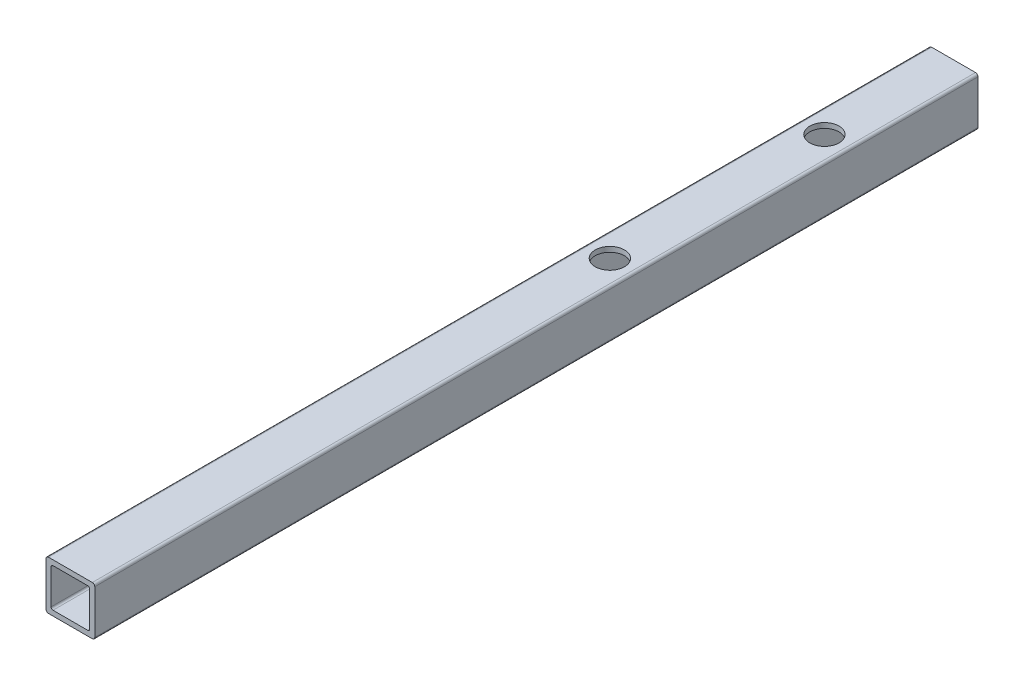
SolidWorks part; units mm, degrees
ref_plane "Front" through (0, 0, 0) normal (0, 0, 1) x (1, 0, 0)
ref_plane "Top" through (0, 0, 0) normal (0, 1, 0) x (1, 0, 0)
ref_plane "Right" through (0, 0, 0) normal (1, 0, 0) x (0, 0, -1)
sketch "Sketch1" plane through (0, 0, 0) normal (0, 0, 1) x (1, 0, 0)
  line L0 (-6.2865, 0) -> (-7.9375, 0) construction
  line L1 (7.1438, -7.9375) -> (-7.1437, -7.9375)
  line L2 (7.9375, -7.1437) -> (7.9375, 7.1437)
  line L3 (7.1438, 7.9375) -> (-7.1437, 7.9375)
  line L4 (-7.9375, -7.1438) -> (-7.9375, 7.1438)
  line L5 (7.9375, -7.9375) -> (-7.9375, 7.9375) construction
  line L6 (7.9375, 7.9375) -> (-7.9375, -7.9375) construction
  line L7 (5.6579, 6.2865) -> (-5.6579, 6.2865)
  line L8 (6.2865, 5.6578) -> (6.2865, -5.6578)
  line L9 (5.6579, -6.2865) -> (-5.6579, -6.2865)
  line L10 (-6.2865, 5.6578) -> (-6.2865, -5.6579)
  line L11 (6.2865, 6.2865) -> (-6.2865, -6.2865) construction
  line L12 (6.2865, -6.2865) -> (-6.2865, 6.2865) construction
  line L13 (0, -6.2865) -> (0, -7.9375) construction
  line L14 (6.2865, -5.6578) -> (6.2865, -7.9375) construction
  line L15 (6.2865, 0) -> (7.9375, 0) construction
  line L16 (6.2865, -7.9375) -> (7.9375, -7.9375) construction
  arc A0 (-5.6579, -6.2865) -> (-6.2865, -5.6579) centre (-5.6579, -5.6579) cw
  arc A1 (6.2865, -5.6578) -> (5.6579, -6.2865) centre (5.6579, -5.6578) cw
  arc A2 (5.6579, 6.2865) -> (6.2865, 5.6578) centre (5.6579, 5.6578) cw
  arc A3 (-5.6579, 6.2865) -> (-6.2865, 5.6578) centre (-5.6579, 5.6578) ccw
  arc A4 (7.1438, -7.9375) -> (7.9375, -7.1437) centre (7.1438, -7.1437) ccw
  arc A5 (7.9375, 7.1437) -> (7.1438, 7.9375) centre (7.1438, 7.1437) ccw
  arc A6 (-7.1437, 7.9375) -> (-7.9375, 7.1438) centre (-7.1437, 7.1438) ccw
  arc A7 (-7.1437, -7.9375) -> (-7.9375, -7.1438) centre (-7.1437, -7.1438) cw
  point P0 (0, 0)
  point P6 (0, 0)
  dimension "D2" = 0.6287
  dimension "D3" = 0.7937
  dimension "Outside Width" = 15.875
  dimension "Ouside Height" = 15.875
  dimension "Wall Thickness" = 1.651
sketch "Sketch2" plane through (0, 0, 0) normal (1, 0, 0) x (0, 0, -1)
  line L0 (-457.2, 0) -> (457.2, 0) construction
  dimension "Length" = 914.4
ref_plane "Plane1" through (7.9375, 0, 0) normal (1, 0, 0) x (0, 0, -1)
sketch "Sketch5" plane through (7.9375, 0, 0) normal (1, 0, 0) x (0, 0, -1)
  line L0 (-457.2, 7.9375) -> (-457.2, -7.9375) construction
  line L1 (457.2, 7.9375) -> (457.2, -7.9375) construction
sketch "Sketch4" plane through (0, 0, 0) normal (0, 0, 1) x (1, 0, 0)
  line L0 (7.9375, -7.1437) -> (7.9375, 7.1437) construction
  line L1 (7.1438, 7.9375) -> (-7.1437, 7.9375) construction
  line L2 (-7.9375, -7.1438) -> (-7.9375, 7.1438) construction
  line L3 (7.1438, -7.9375) -> (-7.1437, -7.9375) construction
  line L4 (6.2865, 5.6578) -> (6.2865, -5.6578) construction
  line L5 (5.6579, -6.2865) -> (-5.6579, -6.2865) construction
  line L6 (-6.2865, 5.6578) -> (-6.2865, -5.6579) construction
  line L7 (5.6579, 6.2865) -> (-5.6579, 6.2865) construction
  line L8 (7.9375, -7.1437) -> (7.9375, 7.1437)
  line L9 (7.1438, 7.9375) -> (-7.1437, 7.9375)
  line L10 (-7.9375, -7.1438) -> (-7.9375, 7.1438)
  line L11 (7.1438, -7.9375) -> (-7.1437, -7.9375)
  line L12 (6.2865, 5.6578) -> (6.2865, -5.6578)
  line L13 (5.6579, -6.2865) -> (-5.6579, -6.2865)
  line L14 (-6.2865, 5.6578) -> (-6.2865, -5.6579)
  line L15 (5.6579, 6.2865) -> (-5.6579, 6.2865)
  arc A0 (7.9375, 7.1437) -> (7.1438, 7.9375) centre (7.1438, 7.1437) ccw construction
  arc A1 (-7.1437, 7.9375) -> (-7.9375, 7.1438) centre (-7.1437, 7.1438) ccw construction
  arc A2 (-7.9375, -7.1438) -> (-7.1437, -7.9375) centre (-7.1437, -7.1438) ccw construction
  arc A3 (7.1438, -7.9375) -> (7.9375, -7.1437) centre (7.1438, -7.1437) ccw construction
  arc A4 (5.6579, -6.2865) -> (6.2865, -5.6578) centre (5.6579, -5.6578) ccw construction
  arc A5 (-6.2865, -5.6579) -> (-5.6579, -6.2865) centre (-5.6579, -5.6579) ccw construction
  arc A6 (-5.6579, 6.2865) -> (-6.2865, 5.6578) centre (-5.6579, 5.6578) ccw construction
  arc A7 (6.2865, 5.6578) -> (5.6579, 6.2865) centre (5.6579, 5.6578) ccw construction
  arc A8 (7.9375, 7.1437) -> (7.1438, 7.9375) centre (7.1438, 7.1437) ccw
  arc A9 (-7.1437, 7.9375) -> (-7.9375, 7.1438) centre (-7.1437, 7.1438) ccw
  arc A10 (-7.9375, -7.1438) -> (-7.1437, -7.9375) centre (-7.1437, -7.1438) ccw
  arc A11 (7.1438, -7.9375) -> (7.9375, -7.1437) centre (7.1438, -7.1437) ccw
  arc A12 (5.6579, -6.2865) -> (6.2865, -5.6578) centre (5.6579, -5.6578) ccw
  arc A13 (-6.2865, -5.6579) -> (-5.6579, -6.2865) centre (-5.6579, -5.6579) ccw
  arc A14 (-5.6579, 6.2865) -> (-6.2865, 5.6578) centre (-5.6579, 5.6578) ccw
  arc A15 (6.2865, 5.6578) -> (5.6579, 6.2865) centre (5.6579, 5.6578) ccw
extrude "Boss-Extrude1" add sketch "Sketch4" along normal up to vertex (457.2 mm away) and the other way up to vertex (457.2 mm away) up to point (0, 0, 457.2) other way up to point (0, 0, -457.2)
hole_wizard "3/8 (0.375) Diameter Hole1" positions "Sketch6" profile "Sketch7" hole size "3/8" standard "ANSI Inch" end condition through all
sketch "Sketch6" plane through (0, -7.9375, 0) normal (0, -1, 0) x (-1, 0, 0)
  point P0 (0, 415.1312)
sketch "Sketch7" plane through (0, -7.9375, -415.1312) normal (1, 0, 0) x (0, 0, -1)
  line L0 (0, 0) -> (0, 15.875)
  line L1 (0, 15.875) -> (4.7625, 15.875)
  line L2 (4.7625, 15.875) -> (4.7625, 0)
  line L5 (4.7625, 0) -> (0, 0)
  line L11 (0, -6.35) -> (0, 107.95) construction
  dimension "Thru Hole Dia." = 9.525
  dimension "Thru Hole Depth" = 15.875
hole_wizard "3/8 (0.375) Diameter Hole2" positions "Sketch8" profile "Sketch9" hole size "3/8" standard "ANSI Inch" end condition through all
sketch "Sketch8" plane through (0, 7.9375, 0) normal (0, 1, 0) x (1, 0, 0)
  point P0 (0, 345.2813)
sketch "Sketch9" plane through (0, 7.9375, -345.2813) normal (1, 0, 0) x (0, 0, 1)
  line L0 (0, 0) -> (0, 15.875)
  line L1 (0, 15.875) -> (4.7625, 15.875)
  line L2 (4.7625, 15.875) -> (4.7625, 0)
  line L5 (4.7625, 0) -> (0, 0)
  line L11 (0, -6.35) -> (0, 107.95) construction
  dimension "Thru Hole Dia." = 9.525
  dimension "Thru Hole Depth" = 15.875
sketch "Sketch10" plane through (-7.9375, 0, 0) normal (-1, 0, 0) x (0, 0, 1)
  line L1 (607.8324, 40.9029) -> (-169.6335, 40.9029)
  line L2 (607.8324, 40.9029) -> (607.8324, -38.0093)
  line L3 (607.8324, -38.0093) -> (-169.6335, -38.0093)
  line L4 (-169.6335, 40.9029) -> (-169.6335, -38.0093)
extrude "Cut-Extrude1" cut sketch "Sketch10" against normal blind 33.02
equation "\"D3@Sketch1\"=\"Outside Width@Sketch1\"*.05"
equation "\"D2@Sketch1\"=\"D1@Sketch1\"*.05"
